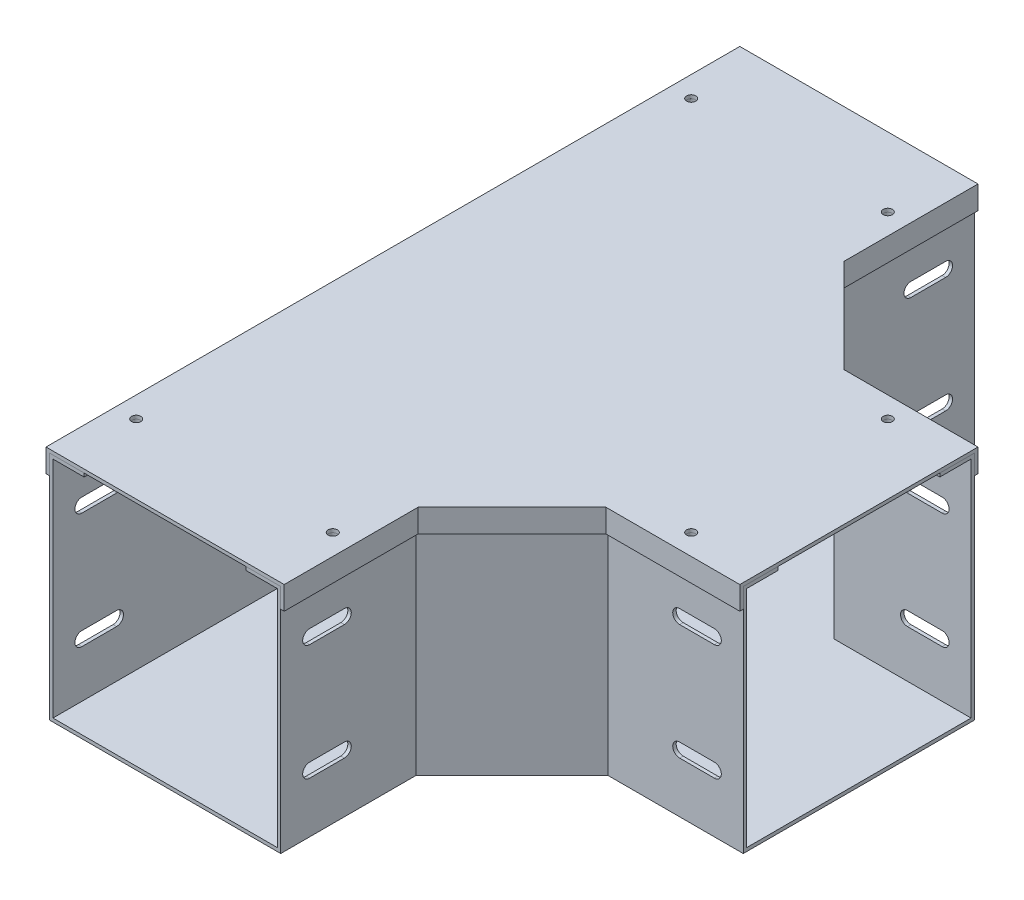
SolidWorks part; units mm, degrees
material "Plain Carbon Steel"
ref_plane "Front Plane" through (0, 0, 0) normal (0, 0, 1) x (1, 0, 0)
ref_plane "Top Plane" through (0, 0, 0) normal (0, 1, 0) x (1, 0, 0)
ref_plane "Right Plane" through (0, 0, 0) normal (1, 0, 0) x (0, 0, -1)
ref_plane "Plane1" through (0, -50, 0) normal (0, 1, 0) x (1, 0, 0)
sketch "Sketch1" plane through (0, -50, 0) normal (0, 1, 0) x (1, 0, 0)
  line L0 (-50, 150) -> (50, 150)
  line L1 (-50, -150) -> (50, -150)
  line L2 (150, 50) -> (150, -50)
  line L3 (-50, 150) -> (-50, -150)
  line L4 (50, -150) -> (50, -91.4214)
  line L5 (150, -50) -> (91.4214, -50)
  line L6 (50, 150) -> (50, 91.4214)
  line L7 (150, 0) -> (-50, 0) construction
  line L8 (91.4214, 50) -> (50, 91.4214)
  line L9 (50, -91.4214) -> (91.4214, -50)
  line L11 (150, 50) -> (91.4214, 50)
  line L12 (0, 150) -> (0, -150) construction
  dimension "Width" = 100
  dimension "Length" = 300
extrude "Boss-Extrude1" add sketch "Sketch1" along normal blind 1.5
sketch "Sketch2" plane through (0, -50, 0) normal (0, -1, 0) x (-1, 0, 0)
  line L0 (-50, -150) -> (-50, -91.4214) construction
  line L1 (-91.4214, -50) -> (-150, -50) construction
  line L2 (-50, -150) -> (-50, -91.4214)
  line L3 (-91.4214, -50) -> (-150, -50)
  line L4 (50, 150) -> (50, -150)
  line L5 (-50, -91.4214) -> (-91.4214, -50)
  line L6 (-150, 50) -> (-91.4214, 50) construction
  line L7 (-50, 91.4214) -> (-50, 150) construction
  line L8 (-150, 50) -> (-91.4214, 50)
  line L9 (-50, 91.4214) -> (-50, 150)
  line L10 (-50, 91.4214) -> (-91.4214, 50)
extrude "Extrude-Thin1" add sketch "Sketch2" against normal blind 100 thin thin type one direction wall 1.5
sketch "Sketch3" plane through (0, 0, 0) normal (0, 0, 1) x (1, 0, 0)
  line L0 (122.5, 25) -> (137.5, 25) construction
  line L1 (122.5, 28) -> (137.5, 28)
  line L2 (122.5, 22) -> (137.5, 22)
  line L3 (122.5, -25) -> (137.5, -25) construction
  line L4 (122.5, -22) -> (137.5, -22)
  line L5 (122.5, -28) -> (137.5, -28)
  line L6 (110, 0) -> (150, 0) construction
  line L7 (150, -48.5) -> (150, 50) construction
  line L9 (130, -50) -> (130, 0) construction
  line L11 (130, 0) -> (130, 50) construction
  arc A0 (122.5, 28) -> (122.5, 22) centre (122.5, 25) ccw
  arc A1 (137.5, 22) -> (137.5, 28) centre (137.5, 25) ccw
  arc A2 (122.5, -22) -> (122.5, -28) centre (122.5, -25) ccw
  arc A3 (137.5, -28) -> (137.5, -22) centre (137.5, -25) ccw
  point P2 (130, 25)
  point P8 (130, -25)
  dimension "D1" = 3
  dimension "D2" = 15
  dimension "D3" = 50
  dimension "D4" = 50
  dimension "D5" = 40
extrude "Cut-Extrude1" cut sketch "Sketch3" against normal through all and the other way through all
sketch "Sketch4" plane through (0, 0, 0) normal (1, 0, 0) x (0, 0, -1)
  line L0 (-150, 0) -> (-110, 0) construction
  line L1 (-150, -48.5) -> (-150, 50) construction
  line L2 (110, 0) -> (150, 0) construction
  line L3 (-130, 50) -> (-130, 0) construction
  line L4 (130, 50) -> (130, 0) construction
  line L5 (-130, 0) -> (-130, -50) construction
  line L6 (130, 0) -> (130, -50) construction
  line L7 (-137.5, 25) -> (-122.5, 25) construction
  line L8 (-137.5, 28) -> (-122.5, 28)
  line L9 (-137.5, 22) -> (-122.5, 22)
  line L10 (-137.5, -25) -> (-122.5, -25) construction
  line L11 (-137.5, -22) -> (-122.5, -22)
  line L12 (-137.5, -28) -> (-122.5, -28)
  line L13 (122.5, 25) -> (137.5, 25) construction
  line L14 (122.5, 28) -> (137.5, 28)
  line L15 (122.5, 22) -> (137.5, 22)
  line L16 (122.5, -25) -> (137.5, -25) construction
  line L17 (122.5, -22) -> (137.5, -22)
  line L18 (122.5, -28) -> (137.5, -28)
  line L19 (150, 50) -> (150, -48.5) construction
  arc A0 (-137.5, 28) -> (-137.5, 22) centre (-137.5, 25) ccw
  arc A1 (-122.5, 22) -> (-122.5, 28) centre (-122.5, 25) ccw
  arc A2 (-137.5, -22) -> (-137.5, -28) centre (-137.5, -25) ccw
  arc A3 (-122.5, -28) -> (-122.5, -22) centre (-122.5, -25) ccw
  arc A4 (122.5, 28) -> (122.5, 22) centre (122.5, 25) ccw
  arc A5 (137.5, 22) -> (137.5, 28) centre (137.5, 25) ccw
  arc A6 (122.5, -22) -> (122.5, -28) centre (122.5, -25) ccw
  arc A7 (137.5, -28) -> (137.5, -22) centre (137.5, -25) ccw
  point P15 (-130, 25)
  point P21 (-130, -25)
  point P29 (130, 25)
  point P35 (130, -25)
  dimension "D1" = 3
  dimension "D2" = 15
  dimension "D3" = 50
  dimension "D4" = 50
  dimension "D5" = 40
extrude "Cut-Extrude2" cut sketch "Sketch4" against normal through all and the other way through all
sketch "Sketch5" plane through (0, 50, 0) normal (0, 1, 0) x (1, 0, 0)
  line L0 (-50, 150) -> (-50, -150) construction
  line L1 (50, -150) -> (50, -91.4214) construction
  line L2 (50, -91.4214) -> (91.4214, -50) construction
  line L3 (91.4214, -50) -> (150, -50) construction
  line L4 (150, 50) -> (91.4214, 50) construction
  line L5 (91.4214, 50) -> (50, 91.4214) construction
  line L6 (50, 91.4214) -> (50, 150) construction
  line L7 (-50, 150) -> (-50, -150)
  line L8 (50, -150) -> (50, -91.4214)
  line L9 (50, -91.4214) -> (91.4214, -50)
  line L10 (91.4214, -50) -> (150, -50)
  line L11 (150, 50) -> (91.4214, 50)
  line L12 (91.4214, 50) -> (50, 91.4214)
  line L13 (50, 91.4214) -> (50, 150)
extrude "Extrude-Thin4" add sketch "Sketch5" against normal blind 1.5 thin thin type one direction reverse wall 15
sketch "Sketch6" plane through (0, 50, 0) normal (0, 1, 0) x (1, 0, 0)
  line L0 (150, -50) -> (150, -35) construction
  line L2 (150, 35) -> (150, 50) construction
  line L3 (-35, 150) -> (-50, 150) construction
  line L4 (50, 150) -> (35, 150) construction
  line L5 (-50, -150) -> (-35, -150) construction
  line L6 (35, -150) -> (50, -150) construction
  circle A0 centre (-42.5, 120) radius 2
  circle A1 centre (-42.5, -120) radius 2
  circle A2 centre (42.5, -120) radius 2
  circle A3 centre (120, -42.5) radius 2
  circle A4 centre (120, 42.5) radius 2
  circle A5 centre (42.5, 120) radius 2
  point P14 (150, -42.5)
  point P16 (-42.5, 150)
  point P18 (150, 42.5)
  point P23 (42.5, 150)
  point P28 (42.5, -150)
  point P29 (-42.5, -150)
  dimension "D1" = 4
  dimension "D2" = 30
  dimension "D3" = 30
  dimension "D4" = 30
extrude "Cut-Extrude3" cut sketch "Sketch6" against normal up to next
sketch "Sketch7" plane through (0, 50, 0) normal (0, 1, 0) x (1, 0, 0)
  line L188 (91.4214, 50) -> (50, 91.4214)
  line L189 (50, 91.4214) -> (50, 150)
  line L190 (50, 150) -> (-50, 150)
  line L191 (-50, 150) -> (-50, -150)
  line L192 (-50, -150) -> (50, -150)
  line L193 (50, -150) -> (50, -91.4214)
  line L194 (50, -91.4214) -> (91.4214, -50)
  line L195 (91.4214, -50) -> (150, -50)
  line L196 (150, -50) -> (150, 50)
  line L197 (150, 50) -> (91.4214, 50)
  line L198 (91.4214, 50) -> (50, 91.4214)
  line L199 (50, 91.4214) -> (50, 150)
  line L200 (50, 150) -> (-50, 150)
  line L201 (-50, 150) -> (-50, -150)
  line L202 (-50, -150) -> (50, -150)
  line L203 (50, -150) -> (50, -91.4214)
  line L204 (50, -91.4214) -> (91.4214, -50)
  line L205 (91.4214, -50) -> (150, -50)
  line L206 (150, -50) -> (150, 50)
  line L207 (150, 50) -> (91.4214, 50)
  dimension "D1" = 0
extrude "Boss-Extrude2" add sketch "Sketch7" along normal blind 1.5 separate body
sketch "Sketch8" plane through (0, 51.5, 0) normal (0, 1, 0) x (1, 0, 0)
  line L10 (150, 50) -> (91.4214, 50)
  line L11 (150, 50) -> (91.4214, 50)
  line L12 (91.4214, 50) -> (50, 91.4214)
  line L13 (91.4214, 50) -> (50, 91.4214)
  line L14 (50, 91.4214) -> (50, 150)
  line L15 (50, 91.4214) -> (50, 150)
  line L16 (50, 150) -> (-50, 150)
  line L18 (-50, 150) -> (-50, -150)
  line L19 (-50, 150) -> (-50, -150)
  line L20 (-50, -150) -> (50, -150)
  line L22 (50, -150) -> (50, -91.4214)
  line L23 (50, -150) -> (50, -91.4214)
  line L24 (50, -91.4214) -> (91.4214, -50)
  line L25 (50, -91.4214) -> (91.4214, -50)
  line L26 (91.4214, -50) -> (150, -50)
  line L27 (91.4214, -50) -> (150, -50)
  line L28 (150, -50) -> (150, 50)
  dimension "D1" = 0
extrude "Extrude-Thin3" add sketch "Sketch8" against normal blind 10 thin thin type one direction wall 1.5
sketch "Sketch9" plane through (0, 51.5, 0) normal (0, 1, 0) x (1, 0, 0)
  circle A1 centre (42.5, 120) radius 2
  circle A2 centre (42.5, 120) radius 2
  circle A3 centre (120, 42.5) radius 2
  circle A4 centre (120, 42.5) radius 2
  circle A5 centre (120, -42.5) radius 2
  circle A6 centre (120, -42.5) radius 2
  circle A7 centre (42.5, -120) radius 2
  circle A8 centre (42.5, -120) radius 2
  circle A9 centre (-42.5, -120) radius 2
  circle A10 centre (-42.5, -120) radius 2
  circle A11 centre (-42.5, 120) radius 2
  circle A12 centre (-42.5, 120) radius 2
  dimension "D1" = 0
  dimension "D2" = 0
  dimension "D3" = 0
  dimension "D4" = 0
  dimension "D5" = 0
  dimension "D6" = 0
extrude "Cut-Extrude4" cut sketch "Sketch9" against normal up to next (1.5 mm away)
sketch "Sketch10" plane through (0, 0, 0) normal (0, -1, 0) x (-1, 0, 0)
  line L0 (50, -150) -> (-50, -150) construction
  line L1 (-150, -50) -> (-150, 50) construction
  line L2 (50, 150) -> (-50, 150) construction
  point P0 (0, -150)
  point P1 (-150, 0)
  point P4 (0, 150)
  point P10 (0, 0)
other "CPoint1" parameters "Diameter"=10, "StubLength"=100
ref_axis "Axis1" through (160, 0, 0) along (-1, 0, 0)
other "CPoint2" parameters "Diameter"=10, "StubLength"=100
ref_axis "Axis3" through (0, 0, 160) along (0, 0, -1)
other "CPoint3" parameters "Diameter"=10, "StubLength"=300
ref_axis "Axis4" through (0, 0, -160) along (0, 0, 1)
other "RPoint1"
equation "\"D5@Extrude-Thin1\"=\"Thickness@Boss-Extrude1\""
equation "\"D3@Sketch3\"=\"Height@Extrude-Thin1\"/2"
equation "\"D4@Sketch3\"=\"Height@Extrude-Thin1\"/2"
equation "\"D3@Sketch4\"=\"Height@Extrude-Thin1\"/2"
equation "\"D4@Sketch4\"=\"Height@Extrude-Thin1\"/2"
equation "\"Thickness@Boss-Extrude2\"=\"Thickness@Boss-Extrude1\""
